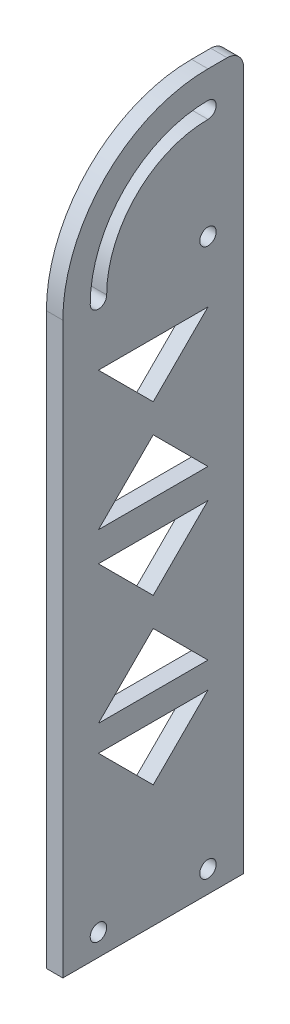
SolidWorks part; units mm, degrees
ref_plane "Front Plane" through (0, 0, 0) normal (0, 0, 1) x (1, 0, 0)
ref_plane "Top Plane" through (0, 0, 0) normal (0, 1, 0) x (1, 0, 0)
ref_plane "Right Plane" through (0, 0, 0) normal (1, 0, 0) x (0, 0, -1)
sketch "Sketch1" plane through (0, 0, 0) normal (1, 0, 0) x (0, 0, -1)
  line L0 (8.8643, 86.5803) -> (13.8643, 86.5803) construction
  line L1 (-14.1357, 86.5803) -> (-19.1357, 86.5803) construction
  line L2 (13.8643, 86.5803) -> (13.8643, 110.0803)
  line L3 (10.8643, 113.0803) -> (7.3643, 113.0803)
  line L4 (7.3643, -14.9197) -> (7.3643, -17.4197) construction
  line L5 (-12.6357, -14.9197) -> (-12.6357, -17.4197) construction
  line L6 (-12.6357, -17.4197) -> (7.3643, -17.4197)
  line L7 (13.8643, 86.5803) -> (13.8643, -17.4197)
  line L8 (13.8643, -17.4197) -> (7.3643, -17.4197)
  line L9 (-19.1357, 86.5803) -> (-19.1357, -17.4197)
  line L10 (-19.1357, -17.4197) -> (-12.6357, -17.4197)
  line L11 (-12.6357, 75.4374) -> (7.3643, 75.4374)
  line L12 (7.3643, 75.4374) -> (-2.6357, 65.4374)
  line L13 (-2.6357, 65.4374) -> (-12.6357, 75.4374)
  line L14 (-2.6357, 60.2115) -> (-12.6357, 50.2115)
  line L15 (-12.6357, 50.2115) -> (7.3643, 50.2115)
  line L16 (7.3643, 50.2115) -> (-2.6357, 60.2115)
  line L17 (-12.6357, 44.8202) -> (7.3643, 44.8202)
  line L18 (7.3643, 44.8202) -> (-2.6357, 34.8202)
  line L19 (-2.6357, 34.8202) -> (-12.6357, 44.8202)
  line L20 (-2.6357, 29.5944) -> (-12.6357, 19.5944)
  line L21 (-12.6357, 19.5944) -> (7.3643, 19.5944)
  line L22 (7.3643, 19.5944) -> (-2.6357, 29.5944)
  line L23 (-12.6357, 14.865) -> (7.3643, 14.865)
  line L24 (7.3643, 14.865) -> (-2.6357, 4.865)
  line L25 (-2.6357, 4.865) -> (-12.6357, 14.865)
  circle A0 centre (-12.6357, -13.4197) radius 1.5
  circle A1 centre (7.3643, -13.4197) radius 1.5
  circle A2 centre (7.3643, 86.5803) radius 1.5
  arc A3 (-14.1357, 86.5803) -> (-11.1357, 86.5803) centre (-12.6357, 86.5803) ccw
  arc A4 (7.3643, 105.0803) -> (7.3643, 108.0803) centre (7.3643, 106.5803) ccw
  arc A5 (7.3643, 105.0803) -> (-11.1357, 86.5803) centre (7.3643, 86.5803) ccw
  arc A6 (7.3643, 108.0803) -> (-14.1357, 86.5803) centre (7.3643, 86.5803) ccw
  arc A7 (-19.1357, 86.5803) -> (7.3643, 113.0803) centre (7.3643, 86.5803) cw
  arc A8 (13.8643, 110.0803) -> (10.8643, 113.0803) centre (10.8643, 110.0803) ccw
  dimension "D1" = 3
  dimension "D2" = 3
  dimension "D4" = 3
  dimension "D6" = 3
  dimension "D7" = 3
  dimension "D12" = 3
  dimension "D3" = 20
  dimension "D5" = 100
  dimension "D8" = 20
  dimension "D9" = 20
  dimension "D10" = 5
  dimension "D11" = 5
  dimension "D13" = 2.5
  dimension "D14" = 2.5
  dimension "D15" = 33
extrude "Boss-Extrude1" add sketch "Sketch1" along normal blind 3
